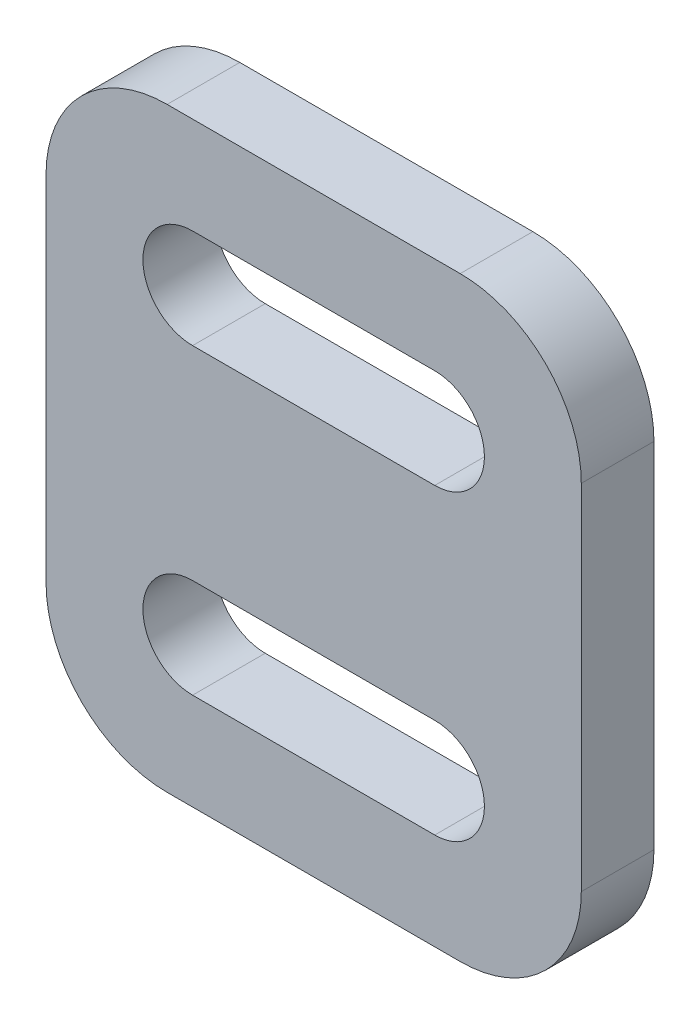
SolidWorks part; units mm, degrees
ref_plane "Plano frontal" through (0, 0, 0) normal (0, 0, 1) x (1, 0, 0)
ref_plane "Plano superior" through (0, 0, 0) normal (0, 1, 0) x (1, 0, 0)
ref_plane "Plano direito" through (0, 0, 0) normal (1, 0, 0) x (0, 0, -1)
sketch "Esboço1" plane through (0, 0, 0) normal (0, 0, 1) x (1, 0, 0)
  line L0 (31.0719, 33.6305) -> (31.0719, 0) construction
  line L1 (16.0719, 26.4418) -> (16.0719, 19.9575) construction
  line L2 (20, 33.6305) -> (31.0719, 33.6305)
  line L3 (20, 40.9805) -> (8.8219, 19.9575) construction
  line L4 (31.0719, 0) -> (14.25, 0) construction
  line L5 (31.0719, 26.5) -> (16.0719, 26.5) construction
  line L6 (22.1219, 26.5) -> (22.1219, 14) construction
  line L9 (38.1719, 7.95) -> (16.0719, 7.95)
  line L10 (38.1719, 7.95) -> (38.1719, 32.55)
  line L11 (38.1719, 32.55) -> (16.0719, 32.55)
  line L12 (16.0719, 7.95) -> (16.0719, 32.55)
  line L13 (38.1719, 7.95) -> (16.0719, 32.55) construction
  line L14 (38.1719, 32.55) -> (16.0719, 7.95) construction
  line L15 (22.1219, 26.5) -> (32.1219, 26.5) construction
  line L16 (22.1219, 28.55) -> (32.1219, 28.55)
  line L17 (22.1219, 24.45) -> (32.1219, 24.45)
  line L18 (22.1219, 14) -> (32.1219, 14) construction
  line L19 (22.1219, 16.05) -> (32.1219, 16.05)
  line L20 (22.1219, 11.95) -> (32.1219, 11.95)
  circle A0 centre (0, 0) radius 7.25 construction
  circle A1 centre (0, 0) radius 14.25 construction
  circle A2 centre (20, 40.9805) radius 23.81 construction
  arc A3 (20, 33.6305) -> (20, 48.3305) centre (20, 40.9805) cw construction
  arc A4 (20, 48.3305) -> (20, 56.0405) centre (20, 52.1855) ccw construction
  circle A5 centre (8.8219, 19.9575) radius 7.25 construction
  arc A6 (16.0719, 19.9575) -> (5.6354, 13.0883) centre (8.5931, 19.9575) cw construction
  arc A7 (20, 56.0405) -> (16.0719, 26.4418) centre (20, 40.9805) ccw construction
  arc A10 (22.1219, 28.55) -> (22.1219, 24.45) centre (22.1219, 26.5) ccw
  arc A11 (32.1219, 24.45) -> (32.1219, 28.55) centre (32.1219, 26.5) ccw
  arc A12 (22.1219, 16.05) -> (22.1219, 11.95) centre (22.1219, 14) ccw
  arc A13 (32.1219, 11.95) -> (32.1219, 16.05) centre (32.1219, 14) ccw
  point P4 (12.2256, 26.3589)
  point P5 (-7.25, 0)
  point P6 (-14.25, 0)
  point P8 (12.9298, 27.6833)
  point P25 (22.1219, 20.25)
  point P26 (27.1219, 20.25)
  point P35 (27.1219, 26.5)
  point P39 (22.1219, 11.95)
  point P42 (27.1219, 14)
  point P48 (34.1719, 26.5)
  point P51 (27.1219, 32.55)
  dimension "D1" = 7.35
  dimension "D2" = 14.5
  dimension "D6" = 47.62
  dimension "D10" = 2.05
  dimension "D3" = 7
  dimension "D4" = 1.5
  dimension "D5" = 45.6004
  dimension "D7" = 28
  dimension "D8" = 15
  dimension "D9" = 20
  dimension "D11" = 12.5
  dimension "D12" = 14
  dimension "D13" = 4
  dimension "D14" = 4
  dimension "D15" = 10
extrude "Ressalto-extrusão1" add sketch "Esboço1" along normal blind 3 contours A4 A7 L1 A6 A1 L0 L2 A3 | A1 A0 | L12 L9 L10 L11 A13 L20 A12 L19 A11 L17 A10 L16 region at (27.1219, 20.25, 0)
fillet "Filete1" radius 5 4 edges at (16.0719, 32.55, 1.5) (16.0719, 7.95, 1.5) (38.1719, 7.95, 1.5) (38.1719, 32.55, 1.5)
